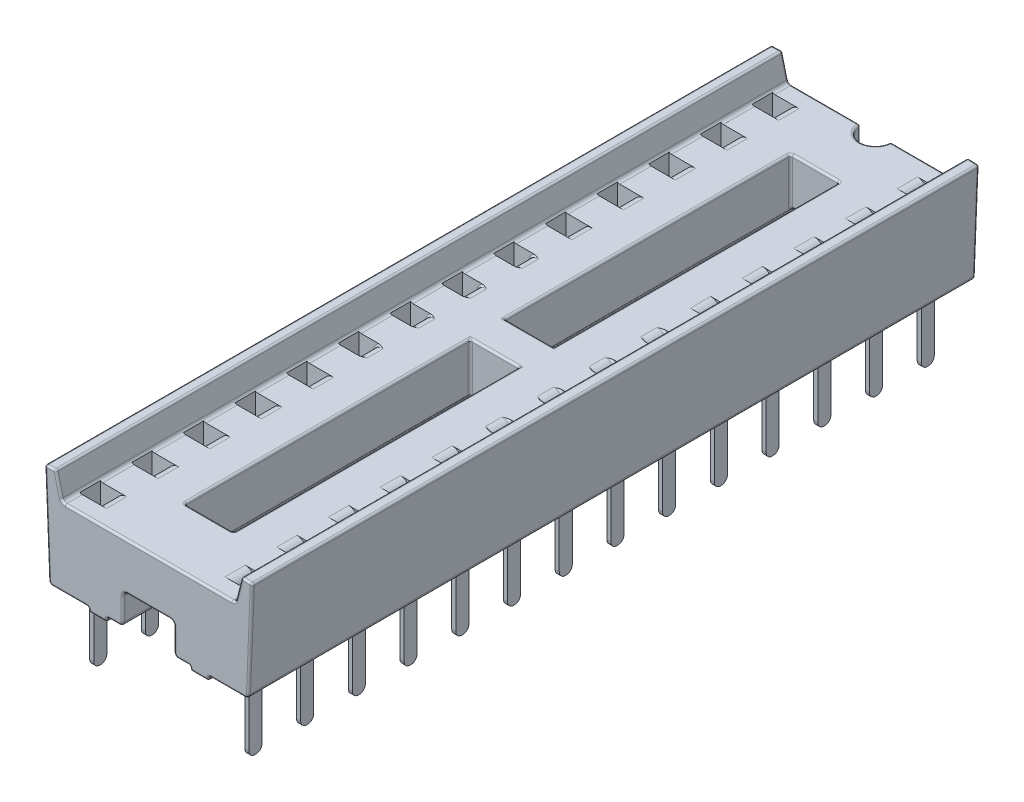
SolidWorks part; units mm, degrees
material "ABS"
ref_plane "Front Plane" through (0, 0, 0) normal (0, 0, 1) x (1, 0, 0)
ref_plane "Top Plane" through (0, 0, 0) normal (0, 1, 0) x (1, 0, 0)
ref_plane "Right Plane" through (0, 0, 0) normal (1, 0, 0) x (0, 0, -1)
sketch "Sketch1" plane through (0, 0, 0) normal (0, 0, 1) x (1, 0, 0)
  line L0 (-2.05, 0) -> (2.05, 0) construction
  line L1 (2.05, 0) -> (2.95, 0)
  line L2 (-2.05, 0) -> (-2.95, 0)
  line L3 (2.95, 0) -> (2.95, 0.2)
  line L4 (2.95, 0.2) -> (4.9, 0.2)
  line L5 (-2.95, 0) -> (-2.95, 0.2)
  line L6 (-2.95, 0.2) -> (-4.9, 0.2)
  line L7 (-2.05, 0) -> (-2.05, 0.2)
  line L8 (-2.05, 0.2) -> (-2.95, 0.2) construction
  line L9 (2.05, 0) -> (2.05, 0.2)
  line L10 (2.05, 0.2) -> (2.95, 0.2) construction
  line L11 (0, 0) -> (0, 1.7) construction
  line L12 (-1.25, 1.7) -> (1.25, 1.7)
  line L13 (-1.25, 1.7) -> (-1.25, 0.2)
  line L14 (-1.25, 0.2) -> (-2.05, 0.2)
  line L15 (1.25, 1.7) -> (1.25, 0.2)
  line L16 (1.25, 0.2) -> (2.05, 0.2)
  line L17 (-5.1, 5.2) -> (-4.5604, 5.2216)
  line L18 (-5.1, 5.2) -> (-5.1, 0.2) construction
  line L19 (-5.1, 0.2) -> (-4.9, 0.2) construction
  line L20 (4.9, 0.2) -> (5.1, 0.2) construction
  line L21 (-5.1, 5.2) -> (-4.9, 0.2)
  line L22 (4.9, 0.2) -> (5.1, 5.2)
  line L23 (5.1, 5.2) -> (5.1, 0.2) construction
  line L24 (5.1, 5.2) -> (4.5604, 5.2216)
  line L25 (0, 1.7) -> (0, 4) construction
  line L26 (-4.25, 4) -> (4.25, 4)
  line L27 (-4.5604, 5.2216) -> (-4.25, 4)
  line L28 (4.5604, 5.2216) -> (4.25, 4)
  dimension "D1" = 4.1
  dimension "D2" = 9.8
  dimension "D3" = 0.9
  dimension "D4" = 2.5
  dimension "D5" = 1.5
  dimension "D6" = 0.2
  dimension "D7" = 10.2
  dimension "D8" = 5
  dimension "D9" = 0.54
  dimension "D10" = 4
  dimension "D11" = 8.5
extrude "Boss-Extrude1" add sketch "Sketch1" along normal mid plane 35.7
fillet "Fillet5" radius 0.2 8 edges at (1.25, 0.2, 0) (4.9, 0.2, 0) (-4.9, 0.2, 0) (-1.25, 0.2, 0) (-1.25, 1.7, 0) (1.25, 1.7, 0) (4.25, 4, 0) (-4.25, 4, 0)
sketch "Sketch2" plane through (0, 4, 0) normal (0, 1, 0) x (1, 0, 0)
  line L1 (0, 0) -> (0, 17.85) construction
  line L2 (-1.2, 14.875) -> (1.2, 14.875)
  line L3 (-1.2, 14.875) -> (-1.2, -14.875)
  line L4 (-1.2, -14.875) -> (1.2, -14.875)
  line L5 (1.2, 14.875) -> (1.2, -14.875)
  line L6 (-1.2, 14.875) -> (1.2, -14.875) construction
  line L7 (-1.2, -14.875) -> (1.2, 14.875) construction
  line L8 (4.0945, 17.85) -> (-4.0945, 17.85) construction
  circle A0 centre (0, 17.85) radius 0.75
  point P2 (0, 0)
  dimension "D1" = 1.5
  dimension "D2" = 29.75
  dimension "D3" = 2.4
extrude "Cut-Extrude1" cut sketch "Sketch2" against normal up to surface (4 mm away) up to face at (-2.5, 0, 0)
sketch "Sketch3" plane through (0, 4, 0) normal (0, 1, 0) x (1, 0, 0)
  line L0 (0, 1.27) -> (0, -1.27) construction
  line L1 (0, 1.27) -> (0, 3.81) construction
  line L2 (0, -1.27) -> (0, -3.81) construction
  line L3 (-3.81, 1.27) -> (3.81, 1.27) construction
  line L4 (3.81, -1.27) -> (-3.81, -1.27) construction
  line L5 (-3.81, -3.81) -> (3.81, -3.81) construction
  line L6 (-3.81, 3.81) -> (3.81, 3.81) construction
  line L7 (0, 3.81) -> (0, 6.35) construction
  line L8 (-4.21, 4.31) -> (-3.41, 4.31)
  line L9 (-4.21, 4.31) -> (-4.21, 3.31)
  line L10 (-4.21, 3.31) -> (-3.41, 3.31)
  line L11 (-3.41, 4.31) -> (-3.41, 3.31)
  line L12 (-4.21, 4.31) -> (-3.41, 3.31) construction
  line L13 (-4.21, 3.31) -> (-3.41, 4.31) construction
  line L14 (-4.21, 1.77) -> (-3.41, 1.77)
  line L15 (-4.21, 1.77) -> (-4.21, 0.77)
  line L16 (-4.21, 0.77) -> (-3.41, 0.77)
  line L17 (-3.41, 1.77) -> (-3.41, 0.77)
  line L18 (-4.21, 1.77) -> (-3.41, 0.77) construction
  line L19 (-4.21, 0.77) -> (-3.41, 1.77) construction
  line L20 (-4.21, -0.77) -> (-3.41, -0.77)
  line L21 (-4.21, -0.77) -> (-4.21, -1.77)
  line L22 (-4.21, -1.77) -> (-3.41, -1.77)
  line L23 (-3.41, -0.77) -> (-3.41, -1.77)
  line L24 (-4.21, -0.77) -> (-3.41, -1.77) construction
  line L25 (-4.21, -1.77) -> (-3.41, -0.77) construction
  line L26 (-4.21, -3.31) -> (-3.41, -3.31)
  line L27 (-4.21, -3.31) -> (-4.21, -4.31)
  line L28 (-4.21, -4.31) -> (-3.41, -4.31)
  line L29 (-3.41, -3.31) -> (-3.41, -4.31)
  line L30 (-4.21, -3.31) -> (-3.41, -4.31) construction
  line L31 (-4.21, -4.31) -> (-3.41, -3.31) construction
  line L32 (4.21, -3.31) -> (3.41, -3.31)
  line L33 (4.21, -3.31) -> (4.21, -4.31)
  line L34 (4.21, -4.31) -> (3.41, -4.31)
  line L35 (3.41, -3.31) -> (3.41, -4.31)
  line L36 (4.21, -3.31) -> (3.41, -4.31) construction
  line L37 (4.21, -4.31) -> (3.41, -3.31) construction
  line L38 (4.21, -0.77) -> (3.41, -0.77)
  line L39 (4.21, -0.77) -> (4.21, -1.77)
  line L40 (4.21, -1.77) -> (3.41, -1.77)
  line L41 (3.41, -0.77) -> (3.41, -1.77)
  line L42 (4.21, -0.77) -> (3.41, -1.77) construction
  line L43 (4.21, -1.77) -> (3.41, -0.77) construction
  line L44 (4.21, 1.77) -> (3.41, 1.77)
  line L45 (4.21, 1.77) -> (4.21, 0.77)
  line L46 (4.21, 0.77) -> (3.41, 0.77)
  line L47 (3.41, 1.77) -> (3.41, 0.77)
  line L48 (4.21, 1.77) -> (3.41, 0.77) construction
  line L49 (4.21, 0.77) -> (3.41, 1.77) construction
  line L50 (4.21, 4.31) -> (3.41, 4.31)
  line L51 (4.21, 4.31) -> (4.21, 3.31)
  line L52 (4.21, 3.31) -> (3.41, 3.31)
  line L53 (3.41, 4.31) -> (3.41, 3.31)
  line L54 (4.21, 4.31) -> (3.41, 3.31) construction
  line L55 (4.21, 3.31) -> (3.41, 4.31) construction
  line L56 (0, 6.35) -> (0, 8.89) construction
  line L57 (0, 8.89) -> (0, 11.43) construction
  line L58 (0, 11.43) -> (0, 13.97) construction
  line L59 (0, 13.97) -> (0, 16.51) construction
  line L60 (0, -3.81) -> (0, -6.35) construction
  line L61 (0, -6.35) -> (0, -8.89) construction
  line L62 (0, -8.89) -> (0, -11.43) construction
  line L63 (0, -11.43) -> (0, -13.97) construction
  line L64 (0, -13.97) -> (0, -16.51) construction
  line L65 (-3.81, -6.35) -> (3.81, -6.35) construction
  line L66 (-3.81, -8.89) -> (3.81, -8.89) construction
  line L67 (-3.81, -11.43) -> (3.81, -11.43) construction
  line L68 (-3.81, -13.97) -> (3.81, -13.97) construction
  line L69 (-3.81, -16.51) -> (3.81, -16.51) construction
  line L70 (-3.81, 6.35) -> (3.81, 6.35) construction
  line L71 (-3.81, 8.89) -> (3.81, 8.89) construction
  line L72 (-3.81, 11.43) -> (3.81, 11.43) construction
  line L73 (-3.81, 13.97) -> (3.81, 13.97) construction
  line L74 (-3.81, 16.51) -> (3.81, 16.51) construction
  line L76 (4.21, -5.85) -> (3.41, -5.85)
  line L77 (4.21, -5.85) -> (4.21, -6.85)
  line L78 (4.21, -6.85) -> (3.41, -6.85)
  line L79 (3.41, -5.85) -> (3.41, -6.85)
  line L80 (4.21, -5.85) -> (3.41, -6.85) construction
  line L81 (4.21, -6.85) -> (3.41, -5.85) construction
  line L82 (4.21, -8.39) -> (3.41, -8.39)
  line L83 (4.21, -8.39) -> (4.21, -9.39)
  line L84 (4.21, -9.39) -> (3.41, -9.39)
  line L85 (3.41, -8.39) -> (3.41, -9.39)
  line L86 (4.21, -8.39) -> (3.41, -9.39) construction
  line L87 (4.21, -9.39) -> (3.41, -8.39) construction
  line L88 (4.21, -10.93) -> (3.41, -10.93)
  line L89 (4.21, -10.93) -> (4.21, -11.93)
  line L90 (4.21, -11.93) -> (3.41, -11.93)
  line L91 (3.41, -10.93) -> (3.41, -11.93)
  line L92 (4.21, -10.93) -> (3.41, -11.93) construction
  line L93 (4.21, -11.93) -> (3.41, -10.93) construction
  line L94 (4.21, -13.47) -> (3.41, -13.47)
  line L95 (4.21, -13.47) -> (4.21, -14.47)
  line L96 (4.21, -14.47) -> (3.41, -14.47)
  line L97 (3.41, -13.47) -> (3.41, -14.47)
  line L98 (4.21, -13.47) -> (3.41, -14.47) construction
  line L99 (4.21, -14.47) -> (3.41, -13.47) construction
  line L100 (4.21, -16.01) -> (3.41, -16.01)
  line L101 (4.21, -16.01) -> (4.21, -17.01)
  line L102 (4.21, -17.01) -> (3.41, -17.01)
  line L103 (3.41, -16.01) -> (3.41, -17.01)
  line L104 (4.21, -16.01) -> (3.41, -17.01) construction
  line L105 (4.21, -17.01) -> (3.41, -16.01) construction
  line L106 (-4.21, -5.85) -> (-3.41, -5.85)
  line L107 (-4.21, -5.85) -> (-4.21, -6.85)
  line L108 (-4.21, -6.85) -> (-3.41, -6.85)
  line L109 (-3.41, -5.85) -> (-3.41, -6.85)
  line L110 (-4.21, -5.85) -> (-3.41, -6.85) construction
  line L111 (-4.21, -6.85) -> (-3.41, -5.85) construction
  line L112 (-4.21, -8.39) -> (-3.41, -8.39)
  line L113 (-4.21, -8.39) -> (-4.21, -9.39)
  line L114 (-4.21, -9.39) -> (-3.41, -9.39)
  line L115 (-3.41, -8.39) -> (-3.41, -9.39)
  line L116 (-4.21, -8.39) -> (-3.41, -9.39) construction
  line L117 (-4.21, -9.39) -> (-3.41, -8.39) construction
  line L118 (-4.21, -10.93) -> (-3.41, -10.93)
  line L119 (-4.21, -10.93) -> (-4.21, -11.93)
  line L120 (-4.21, -11.93) -> (-3.41, -11.93)
  line L121 (-3.41, -10.93) -> (-3.41, -11.93)
  line L122 (-4.21, -10.93) -> (-3.41, -11.93) construction
  line L123 (-4.21, -11.93) -> (-3.41, -10.93) construction
  line L124 (-4.21, -13.47) -> (-3.41, -13.47)
  line L125 (-4.21, -13.47) -> (-4.21, -14.47)
  line L126 (-4.21, -14.47) -> (-3.41, -14.47)
  line L127 (-3.41, -13.47) -> (-3.41, -14.47)
  line L128 (-4.21, -13.47) -> (-3.41, -14.47) construction
  line L129 (-4.21, -14.47) -> (-3.41, -13.47) construction
  line L130 (-4.21, -16.01) -> (-3.41, -16.01)
  line L131 (-4.21, -16.01) -> (-4.21, -17.01)
  line L132 (-4.21, -17.01) -> (-3.41, -17.01)
  line L133 (-3.41, -16.01) -> (-3.41, -17.01)
  line L134 (-4.21, -16.01) -> (-3.41, -17.01) construction
  line L135 (-4.21, -17.01) -> (-3.41, -16.01) construction
  line L136 (-4.21, 6.85) -> (-3.41, 6.85)
  line L137 (-4.21, 6.85) -> (-4.21, 5.85)
  line L138 (-4.21, 5.85) -> (-3.41, 5.85)
  line L139 (-3.41, 6.85) -> (-3.41, 5.85)
  line L140 (-4.21, 6.85) -> (-3.41, 5.85) construction
  line L141 (-4.21, 5.85) -> (-3.41, 6.85) construction
  line L142 (4.21, 6.85) -> (3.41, 6.85)
  line L143 (4.21, 6.85) -> (4.21, 5.85)
  line L144 (4.21, 5.85) -> (3.41, 5.85)
  line L145 (3.41, 6.85) -> (3.41, 5.85)
  line L146 (4.21, 6.85) -> (3.41, 5.85) construction
  line L147 (4.21, 5.85) -> (3.41, 6.85) construction
  line L148 (4.21, 9.39) -> (3.41, 9.39)
  line L149 (4.21, 9.39) -> (4.21, 8.39)
  line L150 (4.21, 8.39) -> (3.41, 8.39)
  line L151 (3.41, 9.39) -> (3.41, 8.39)
  line L152 (4.21, 9.39) -> (3.41, 8.39) construction
  line L153 (4.21, 8.39) -> (3.41, 9.39) construction
  line L154 (4.21, 11.93) -> (3.41, 11.93)
  line L155 (4.21, 11.93) -> (4.21, 10.93)
  line L156 (4.21, 10.93) -> (3.41, 10.93)
  line L157 (3.41, 11.93) -> (3.41, 10.93)
  line L158 (4.21, 11.93) -> (3.41, 10.93) construction
  line L159 (4.21, 10.93) -> (3.41, 11.93) construction
  line L160 (-4.21, 9.39) -> (-3.41, 9.39)
  line L161 (-4.21, 9.39) -> (-4.21, 8.39)
  line L162 (-4.21, 8.39) -> (-3.41, 8.39)
  line L163 (-3.41, 9.39) -> (-3.41, 8.39)
  line L164 (-4.21, 9.39) -> (-3.41, 8.39) construction
  line L165 (-4.21, 8.39) -> (-3.41, 9.39) construction
  line L166 (-4.21, 11.93) -> (-3.41, 11.93)
  line L167 (-4.21, 11.93) -> (-4.21, 10.93)
  line L168 (-4.21, 10.93) -> (-3.41, 10.93)
  line L169 (-3.41, 11.93) -> (-3.41, 10.93)
  line L170 (-4.21, 11.93) -> (-3.41, 10.93) construction
  line L171 (-4.21, 10.93) -> (-3.41, 11.93) construction
  line L172 (-4.21, 14.47) -> (-3.41, 14.47)
  line L173 (-4.21, 14.47) -> (-4.21, 13.47)
  line L174 (-4.21, 13.47) -> (-3.41, 13.47)
  line L175 (-3.41, 14.47) -> (-3.41, 13.47)
  line L176 (-4.21, 14.47) -> (-3.41, 13.47) construction
  line L177 (-4.21, 13.47) -> (-3.41, 14.47) construction
  line L178 (4.21, 14.47) -> (3.41, 14.47)
  line L179 (4.21, 14.47) -> (4.21, 13.47)
  line L180 (4.21, 13.47) -> (3.41, 13.47)
  line L181 (3.41, 14.47) -> (3.41, 13.47)
  line L182 (4.21, 14.47) -> (3.41, 13.47) construction
  line L183 (4.21, 13.47) -> (3.41, 14.47) construction
  line L184 (-4.21, 17.01) -> (-3.41, 17.01)
  line L185 (-4.21, 17.01) -> (-4.21, 16.01)
  line L186 (-4.21, 16.01) -> (-3.41, 16.01)
  line L187 (-3.41, 17.01) -> (-3.41, 16.01)
  line L188 (-4.21, 17.01) -> (-3.41, 16.01) construction
  line L189 (-4.21, 16.01) -> (-3.41, 17.01) construction
  line L190 (4.21, 17.01) -> (3.41, 17.01)
  line L191 (4.21, 17.01) -> (4.21, 16.01)
  line L192 (4.21, 16.01) -> (3.41, 16.01)
  line L193 (3.41, 17.01) -> (3.41, 16.01)
  line L194 (4.21, 17.01) -> (3.41, 16.01) construction
  line L195 (4.21, 16.01) -> (3.41, 17.01) construction
  dimension "D1" = 2.54
  dimension "D2" = 7.62
  dimension "D3" = 0.8
  dimension "D4" = 1
extrude "Cut-Extrude2" cut sketch "Sketch3" against normal blind 3 and the other way through all
fillet "Fillet6" radius 0.1 12 edges at (-1.2, 2.8161, 14.875) (1.2, 2.8161, 14.875) (1.2, 2.8161, -14.875) (-1.2, 2.8161, -14.875) (-2.95, 0, 0) (-2.05, 0, 0) (2.05, 0, 0) (2.95, 0, 0) (5.1, 5.2, 0) (4.5604, 5.2216, 0) (-5.1, 5.2, 0) (-4.5604, 5.2216, 0)
fillet "Fillet7" radius 0.5 28 edges at (3.41, 4, -3.81) (3.41, 4, -1.27) (3.41, 4, 1.27) (3.41, 4, 3.81) (-3.41, 4, 3.81) (-3.41, 4, 1.27) (-3.41, 4, -1.27) (-3.41, 4, -3.81) (3.41, 4, -6.35) (3.41, 4, -8.89) (3.41, 4, -11.43) (3.41, 4, -13.97) (3.41, 4, -16.51) (-3.41, 4, -16.51) (3.41, 4, 16.51) (3.41, 4, 13.97) (3.41, 4, 11.43) (3.41, 4, 8.89) (3.41, 4, 6.35) (-3.41, 4, 16.51) (-3.41, 4, 13.97) (-3.41, 4, 11.43) (-3.41, 4, 8.89) (-3.41, 4, 6.35) (-3.41, 4, -13.97) (-3.41, 4, -11.43) (-3.41, 4, -8.89) (-3.41, 4, -6.35)
fillet "Fillet8" radius 0.1 6 edges at (2.95, 0.2, 0) (2.05, 0.2, 0) (-2.05, 0.2, 0) (-2.95, 0.2, 0) (-0.75, 2.85, -17.85) (0.75, 2.85, -17.85)
fillet "Fillet10" radius 0.1 132 edges at (3.41, 2.25, 4.31) (3.41, 2.25, 3.31) (3.41, 2.25, 1.77) (3.41, 2.25, 0.77) (3.41, 2.25, -0.77) (3.41, 2.25, -1.77) (3.41, 2.25, -3.31) (3.41, 2.25, -4.31) (-3.41, 2.25, -4.31) (-3.41, 2.25, -3.31) (-3.41, 2.25, -0.77) (-3.41, 2.25, -1.77) (-3.41, 2.25, 0.77) (-3.41, 2.25, 1.77) (-3.41, 2.25, 4.31) (-3.41, 2.25, 3.31) (1.0752, 1.6984, -14.875) (1.1867, 1.646, -14.8249) (1.2, 1.6323, 0) (1.1844, 1.6481, 14.8287) (1.0752, 1.6984, 14.875) (0, 1.7, 14.875) (-1.0752, 1.6984, 14.875) (-1.1867, 1.646, 14.8249) (-1.2, 1.6323, 0) (-1.1844, 1.6481, -14.8287) (-1.0752, 1.6984, -14.875) (-1.1707, 4, -14.8457) (0, 4, -14.875) (1.1707, 4, -14.8457) (1.2, 4, 0) (1.1707, 4, 14.8457) (0, 4, 14.875) (-1.1707, 4, 14.8457) (4.2172, 4.0421, 17.85) (4.4144, 4.6469, 17.85) (4.5776, 5.1986, 17.85) (4.8207, 5.2112, 17.85) (5.0696, 5.1719, 17.85) (5.0018, 2.746, 17.85) (4.8464, 0.2558, 17.85) (3.8789, 0.2, 17.85) (2.9793, 0.1707, 17.85) (2.9207, 0.0293, 17.85) (2.5, 0, 17.85) (2.0793, 0.0293, 17.85) (2.0207, 0.1707, 17.85) (1.7, 0.2, 17.85) (1.3086, 0.2586, 17.85) (1.25, 0.95, 17.85) (1.1914, 1.6414, 17.85) (0, 1.7, 17.85) (-1.1914, 1.6414, 17.85) (-1.25, 0.95, 17.85) (-1.3086, 0.2586, 17.85) (-1.7, 0.2, 17.85) (-2.0207, 0.1707, 17.85) (-2.0793, 0.0293, 17.85) (-2.5, 0, 17.85) (-2.9207, 0.0293, 17.85) (-2.9793, 0.1707, 17.85) (-3.8789, 0.2, 17.85) (-4.8464, 0.2558, 17.85) (-5.0018, 2.746, 17.85) (-5.0696, 5.1719, 17.85) (-4.8207, 5.2112, 17.85) (-4.5776, 5.1986, 17.85) (-4.4144, 4.6469, 17.85) (-4.2172, 4.0421, 17.85) (4.2172, 4.0421, -17.85) (4.4144, 4.6469, -17.85) (4.5776, 5.1986, -17.85) (4.8207, 5.2112, -17.85) (5.0696, 5.1719, -17.85) (5.0018, 2.746, -17.85) (4.8464, 0.2558, -17.85) (3.8789, 0.2, -17.85) (2.9793, 0.1707, -17.85) (2.9207, 0.0293, -17.85) (2.5, 0, -17.85) (2.0793, 0.0293, -17.85) (2.0207, 0.1707, -17.85) (1.7, 0.2, -17.85) (1.3086, 0.2586, -17.85) (1.25, 0.95, -17.85) (1.1914, 1.6414, -17.85) (0.947, 1.7, -17.85) (0.7777, 1.7, -17.8248) (0, 1.7, -17.1) (-0.7777, 1.7, -17.8248) (-0.947, 1.7, -17.85) (-1.1914, 1.6414, -17.85) (-1.25, 0.95, -17.85) (-1.3086, 0.2586, -17.85) (-1.7, 0.2, -17.85) (-2.0207, 0.1707, -17.85) (-2.0793, 0.0293, -17.85) (-2.5, 0, -17.85) (-2.9207, 0.0293, -17.85) (-2.9793, 0.1707, -17.85) (-3.8789, 0.2, -17.85) (-4.8464, 0.2558, -17.85) (-5.0018, 2.746, -17.85) (-5.0696, 5.1719, -17.85) (-4.8207, 5.2112, -17.85) (-4.5776, 5.1986, -17.85) (-4.4144, 4.6469, -17.85) (-4.2172, 4.0421, -17.85) (-2.4693, 4, -17.85) (-0.7777, 4, -17.8248) (0, 4, -17.1) (0.7777, 4, -17.8248) (3.2636, 3.8536, 4.31) (3.2636, 3.8536, 3.31) (3.2636, 3.8536, 1.77) (3.2636, 3.8536, 0.77) (3.2636, 3.8536, -0.77) (3.2636, 3.8536, -1.77) (3.2636, 3.8536, -3.31) (3.2636, 3.8536, -4.31) (-3.2636, 3.8536, -4.31) (-3.2636, 3.8536, -3.31) (-3.2636, 3.8536, -0.77) (-3.2636, 3.8536, -1.77) (-3.2636, 3.8536, 0.77) (-3.2636, 3.8536, 1.77) (-3.2636, 3.8536, 4.31) (-3.2636, 3.8536, 3.31) (0, 1.7, -14.875) (-1.2, 4, 0) (0, 4, 17.85) (2.4693, 4, -17.85)
sketch "Sketch4" plane through (0, 0.2, 0) normal (0, -1, 0) x (1, 0, 0)
  line L0 (0, 1.27) -> (0, -1.27) construction
  line L1 (0, 1.27) -> (0, 3.81) construction
  line L2 (0, -1.27) -> (0, -3.81) construction
  line L3 (-3.81, 1.27) -> (3.81, 1.27) construction
  line L4 (-3.81, -1.27) -> (3.81, -1.27) construction
  line L5 (-3.81, 3.81) -> (3.81, 3.81) construction
  line L6 (-3.81, -3.81) -> (3.81, -3.81) construction
  line L7 (0, -3.81) -> (0, -6.35) construction
  line L8 (3.71, 4.13) -> (3.91, 4.13)
  line L9 (3.71, 4.13) -> (3.71, 3.49)
  line L10 (3.71, 3.49) -> (3.91, 3.49)
  line L11 (3.91, 4.13) -> (3.91, 3.49)
  line L12 (3.71, 4.13) -> (3.91, 3.49) construction
  line L13 (3.71, 3.49) -> (3.91, 4.13) construction
  line L14 (3.71, 1.59) -> (3.91, 1.59)
  line L15 (3.71, 1.59) -> (3.71, 0.95)
  line L16 (3.71, 0.95) -> (3.91, 0.95)
  line L17 (3.91, 1.59) -> (3.91, 0.95)
  line L18 (3.71, 1.59) -> (3.91, 0.95) construction
  line L19 (3.71, 0.95) -> (3.91, 1.59) construction
  line L20 (3.71, -0.95) -> (3.91, -0.95)
  line L21 (3.71, -0.95) -> (3.71, -1.59)
  line L22 (3.71, -1.59) -> (3.91, -1.59)
  line L23 (3.91, -0.95) -> (3.91, -1.59)
  line L24 (3.71, -0.95) -> (3.91, -1.59) construction
  line L25 (3.71, -1.59) -> (3.91, -0.95) construction
  line L26 (3.71, -3.49) -> (3.91, -3.49)
  line L27 (3.71, -3.49) -> (3.71, -4.13)
  line L28 (3.71, -4.13) -> (3.91, -4.13)
  line L29 (3.91, -3.49) -> (3.91, -4.13)
  line L30 (3.71, -3.49) -> (3.91, -4.13) construction
  line L31 (3.71, -4.13) -> (3.91, -3.49) construction
  line L32 (-3.71, 4.13) -> (-3.91, 4.13)
  line L33 (-3.71, 4.13) -> (-3.71, 3.49)
  line L34 (-3.71, 3.49) -> (-3.91, 3.49)
  line L35 (-3.91, 4.13) -> (-3.91, 3.49)
  line L36 (-3.71, 4.13) -> (-3.91, 3.49) construction
  line L37 (-3.71, 3.49) -> (-3.91, 4.13) construction
  line L38 (-3.71, 1.59) -> (-3.91, 1.59)
  line L39 (-3.71, 1.59) -> (-3.71, 0.95)
  line L40 (-3.71, 0.95) -> (-3.91, 0.95)
  line L41 (-3.91, 1.59) -> (-3.91, 0.95)
  line L42 (-3.71, 1.59) -> (-3.91, 0.95) construction
  line L43 (-3.71, 0.95) -> (-3.91, 1.59) construction
  line L44 (-3.71, -0.95) -> (-3.91, -0.95)
  line L45 (-3.71, -0.95) -> (-3.71, -1.59)
  line L46 (-3.71, -1.59) -> (-3.91, -1.59)
  line L47 (-3.91, -0.95) -> (-3.91, -1.59)
  line L48 (-3.71, -0.95) -> (-3.91, -1.59) construction
  line L49 (-3.71, -1.59) -> (-3.91, -0.95) construction
  line L50 (-3.71, -3.49) -> (-3.91, -3.49)
  line L51 (-3.71, -3.49) -> (-3.71, -4.13)
  line L52 (-3.71, -4.13) -> (-3.91, -4.13)
  line L53 (-3.91, -3.49) -> (-3.91, -4.13)
  line L54 (-3.71, -3.49) -> (-3.91, -4.13) construction
  line L55 (-3.71, -4.13) -> (-3.91, -3.49) construction
  line L56 (0, -6.35) -> (0, -8.89) construction
  line L57 (0, -8.89) -> (0, -11.43) construction
  line L58 (0, -11.43) -> (0, -13.97) construction
  line L59 (0, -13.97) -> (0, -16.51) construction
  line L60 (0, 3.81) -> (0, 6.35) construction
  line L61 (0, 6.35) -> (0, 8.89) construction
  line L62 (0, 8.89) -> (0, 11.43) construction
  line L63 (0, 11.43) -> (0, 13.97) construction
  line L64 (0, 13.97) -> (0, 16.51) construction
  line L65 (-3.81, 6.35) -> (3.81, 6.35) construction
  line L66 (-3.81, 8.89) -> (3.81, 8.89) construction
  line L67 (-3.81, 11.43) -> (3.81, 11.43) construction
  line L68 (-3.81, 13.97) -> (3.81, 13.97) construction
  line L69 (-3.81, 16.51) -> (3.81, 16.51) construction
  line L70 (-3.81, -6.35) -> (3.81, -6.35) construction
  line L71 (-3.81, -8.89) -> (3.81, -8.89) construction
  line L72 (-3.81, -11.43) -> (3.81, -11.43) construction
  line L73 (-3.81, -13.97) -> (3.81, -13.97) construction
  line L74 (-3.81, -16.51) -> (3.81, -16.51) construction
  line L76 (-3.91, -6.03) -> (-3.71, -6.03)
  line L77 (-3.91, -6.03) -> (-3.91, -6.67)
  line L78 (-3.91, -6.67) -> (-3.71, -6.67)
  line L79 (-3.71, -6.03) -> (-3.71, -6.67)
  line L80 (-3.91, -6.03) -> (-3.71, -6.67) construction
  line L81 (-3.91, -6.67) -> (-3.71, -6.03) construction
  line L82 (-3.91, -8.57) -> (-3.71, -8.57)
  line L83 (-3.91, -8.57) -> (-3.91, -9.21)
  line L84 (-3.91, -9.21) -> (-3.71, -9.21)
  line L85 (-3.71, -8.57) -> (-3.71, -9.21)
  line L86 (-3.91, -8.57) -> (-3.71, -9.21) construction
  line L87 (-3.91, -9.21) -> (-3.71, -8.57) construction
  line L88 (-3.91, -11.11) -> (-3.71, -11.11)
  line L89 (-3.91, -11.11) -> (-3.91, -11.75)
  line L90 (-3.91, -11.75) -> (-3.71, -11.75)
  line L91 (-3.71, -11.11) -> (-3.71, -11.75)
  line L92 (-3.91, -11.11) -> (-3.71, -11.75) construction
  line L93 (-3.91, -11.75) -> (-3.71, -11.11) construction
  line L94 (3.71, -6.03) -> (3.91, -6.03)
  line L95 (3.71, -6.03) -> (3.71, -6.67)
  line L96 (3.71, -6.67) -> (3.91, -6.67)
  line L97 (3.91, -6.03) -> (3.91, -6.67)
  line L98 (3.71, -6.03) -> (3.91, -6.67) construction
  line L99 (3.71, -6.67) -> (3.91, -6.03) construction
  line L100 (3.71, -8.57) -> (3.91, -8.57)
  line L101 (3.71, -8.57) -> (3.71, -9.21)
  line L102 (3.71, -9.21) -> (3.91, -9.21)
  line L103 (3.91, -8.57) -> (3.91, -9.21)
  line L104 (3.71, -8.57) -> (3.91, -9.21) construction
  line L105 (3.71, -9.21) -> (3.91, -8.57) construction
  line L106 (3.71, -11.11) -> (3.91, -11.11)
  line L107 (3.71, -11.11) -> (3.71, -11.75)
  line L108 (3.71, -11.75) -> (3.91, -11.75)
  line L109 (3.91, -11.11) -> (3.91, -11.75)
  line L110 (3.71, -11.11) -> (3.91, -11.75) construction
  line L111 (3.71, -11.75) -> (3.91, -11.11) construction
  line L112 (3.71, -13.65) -> (3.91, -13.65)
  line L113 (3.71, -13.65) -> (3.71, -14.29)
  line L114 (3.71, -14.29) -> (3.91, -14.29)
  line L115 (3.91, -13.65) -> (3.91, -14.29)
  line L116 (3.71, -13.65) -> (3.91, -14.29) construction
  line L117 (3.71, -14.29) -> (3.91, -13.65) construction
  line L118 (3.71, -16.19) -> (3.91, -16.19)
  line L119 (3.71, -16.19) -> (3.71, -16.83)
  line L120 (3.71, -16.83) -> (3.91, -16.83)
  line L121 (3.91, -16.19) -> (3.91, -16.83)
  line L122 (3.71, -16.19) -> (3.91, -16.83) construction
  line L123 (3.71, -16.83) -> (3.91, -16.19) construction
  line L124 (-3.71, -13.65) -> (-3.91, -13.65)
  line L125 (-3.71, -13.65) -> (-3.71, -14.29)
  line L126 (-3.71, -14.29) -> (-3.91, -14.29)
  line L127 (-3.91, -13.65) -> (-3.91, -14.29)
  line L128 (-3.71, -13.65) -> (-3.91, -14.29) construction
  line L129 (-3.71, -14.29) -> (-3.91, -13.65) construction
  line L130 (-3.71, -16.19) -> (-3.91, -16.19)
  line L131 (-3.71, -16.19) -> (-3.71, -16.83)
  line L132 (-3.71, -16.83) -> (-3.91, -16.83)
  line L133 (-3.91, -16.19) -> (-3.91, -16.83)
  line L134 (-3.71, -16.19) -> (-3.91, -16.83) construction
  line L135 (-3.71, -16.83) -> (-3.91, -16.19) construction
  line L136 (-3.71, 6.67) -> (-3.91, 6.67)
  line L137 (-3.71, 6.67) -> (-3.71, 6.03)
  line L138 (-3.71, 6.03) -> (-3.91, 6.03)
  line L139 (-3.91, 6.67) -> (-3.91, 6.03)
  line L140 (-3.71, 6.67) -> (-3.91, 6.03) construction
  line L141 (-3.71, 6.03) -> (-3.91, 6.67) construction
  line L142 (3.71, 6.67) -> (3.91, 6.67)
  line L143 (3.71, 6.67) -> (3.71, 6.03)
  line L144 (3.71, 6.03) -> (3.91, 6.03)
  line L145 (3.91, 6.67) -> (3.91, 6.03)
  line L146 (3.71, 6.67) -> (3.91, 6.03) construction
  line L147 (3.71, 6.03) -> (3.91, 6.67) construction
  line L148 (3.71, 9.21) -> (3.91, 9.21)
  line L149 (3.71, 9.21) -> (3.71, 8.57)
  line L150 (3.71, 8.57) -> (3.91, 8.57)
  line L151 (3.91, 9.21) -> (3.91, 8.57)
  line L152 (3.71, 9.21) -> (3.91, 8.57) construction
  line L153 (3.71, 8.57) -> (3.91, 9.21) construction
  line L154 (-3.71, 9.21) -> (-3.91, 9.21)
  line L155 (-3.71, 9.21) -> (-3.71, 8.57)
  line L156 (-3.71, 8.57) -> (-3.91, 8.57)
  line L157 (-3.91, 9.21) -> (-3.91, 8.57)
  line L158 (-3.71, 9.21) -> (-3.91, 8.57) construction
  line L159 (-3.71, 8.57) -> (-3.91, 9.21) construction
  line L160 (-3.71, 11.75) -> (-3.91, 11.75)
  line L161 (-3.71, 11.75) -> (-3.71, 11.11)
  line L162 (-3.71, 11.11) -> (-3.91, 11.11)
  line L163 (-3.91, 11.75) -> (-3.91, 11.11)
  line L164 (-3.71, 11.75) -> (-3.91, 11.11) construction
  line L165 (-3.71, 11.11) -> (-3.91, 11.75) construction
  line L166 (-3.71, 14.29) -> (-3.91, 14.29)
  line L167 (-3.71, 14.29) -> (-3.71, 13.65)
  line L168 (-3.71, 13.65) -> (-3.91, 13.65)
  line L169 (-3.91, 14.29) -> (-3.91, 13.65)
  line L170 (-3.71, 14.29) -> (-3.91, 13.65) construction
  line L171 (-3.71, 13.65) -> (-3.91, 14.29) construction
  line L172 (-3.71, 16.83) -> (-3.91, 16.83)
  line L173 (-3.71, 16.83) -> (-3.71, 16.19)
  line L174 (-3.71, 16.19) -> (-3.91, 16.19)
  line L175 (-3.91, 16.83) -> (-3.91, 16.19)
  line L176 (-3.71, 16.83) -> (-3.91, 16.19) construction
  line L177 (-3.71, 16.19) -> (-3.91, 16.83) construction
  line L178 (3.71, 11.75) -> (3.91, 11.75)
  line L179 (3.71, 11.75) -> (3.71, 11.11)
  line L180 (3.71, 11.11) -> (3.91, 11.11)
  line L181 (3.91, 11.75) -> (3.91, 11.11)
  line L182 (3.71, 11.75) -> (3.91, 11.11) construction
  line L183 (3.71, 11.11) -> (3.91, 11.75) construction
  line L184 (3.71, 14.29) -> (3.91, 14.29)
  line L185 (3.71, 14.29) -> (3.71, 13.65)
  line L186 (3.71, 13.65) -> (3.91, 13.65)
  line L187 (3.91, 14.29) -> (3.91, 13.65)
  line L188 (3.71, 14.29) -> (3.91, 13.65) construction
  line L189 (3.71, 13.65) -> (3.91, 14.29) construction
  line L190 (3.71, 16.83) -> (3.91, 16.83)
  line L191 (3.71, 16.83) -> (3.71, 16.19)
  line L192 (3.71, 16.19) -> (3.91, 16.19)
  line L193 (3.91, 16.83) -> (3.91, 16.19)
  line L194 (3.71, 16.83) -> (3.91, 16.19) construction
  line L195 (3.71, 16.19) -> (3.91, 16.83) construction
  dimension "D1" = 2.54
  dimension "D2" = 0.2
  dimension "D3" = 0.64
  dimension "D4" = 7.62
extrude "Boss-Extrude2" add sketch "Sketch4" along normal blind 3.5
fillet "Fillet11" radius 0.3 56 edges at (3.81, -3.3, 4.13) (3.81, -3.3, 3.49) (3.81, -3.3, 1.59) (3.81, -3.3, 0.95) (3.81, -3.3, -0.95) (3.81, -3.3, -1.59) (3.81, -3.3, -3.49) (3.81, -3.3, -4.13) (-3.81, -3.3, -4.13) (-3.81, -3.3, -3.49) (-3.81, -3.3, -1.59) (-3.81, -3.3, -0.95) (-3.81, -3.3, 0.95) (-3.81, -3.3, 1.59) (-3.81, -3.3, 3.49) (-3.81, -3.3, 4.13) (-3.81, -3.3, -16.83) (-3.81, -3.3, -16.19) (-3.81, -3.3, -14.29) (-3.81, -3.3, -13.65) (-3.81, -3.3, -11.75) (-3.81, -3.3, -11.11) (-3.81, -3.3, -9.21) (-3.81, -3.3, -8.57) (-3.81, -3.3, -6.67) (-3.81, -3.3, -6.03) (-3.81, -3.3, 16.83) (-3.81, -3.3, 16.19) (-3.81, -3.3, 14.29) (-3.81, -3.3, 13.65) (-3.81, -3.3, 11.75) (-3.81, -3.3, 11.11) (-3.81, -3.3, 9.21) (-3.81, -3.3, 8.57) (-3.81, -3.3, 6.67) (-3.81, -3.3, 6.03) (3.81, -3.3, -16.83) (3.81, -3.3, -16.19) (3.81, -3.3, -14.29) (3.81, -3.3, -13.65) (3.81, -3.3, -11.75) (3.81, -3.3, -11.11) (3.81, -3.3, -9.21) (3.81, -3.3, -8.57) (3.81, -3.3, -6.67) (3.81, -3.3, -6.03) (3.81, -3.3, 6.03) (3.81, -3.3, 6.67) (3.81, -3.3, 8.57) (3.81, -3.3, 9.21) (3.81, -3.3, 11.11) (3.81, -3.3, 11.75) (3.81, -3.3, 13.65) (3.81, -3.3, 14.29) (3.81, -3.3, 16.19) (3.81, -3.3, 16.83)
sketch "Sketch5" plane through (0, 4, 0) normal (0, 1, 0) x (1, 0, 0)
  line L1 (-1.7, 0.85) -> (1.7, 0.85)
  line L2 (-1.7, 0.85) -> (-1.7, -0.85)
  line L3 (-1.7, -0.85) -> (1.7, -0.85)
  line L4 (1.7, 0.85) -> (1.7, -0.85)
  line L5 (-1.7, 0.85) -> (1.7, -0.85) construction
  line L6 (-1.7, -0.85) -> (1.7, 0.85) construction
  point P0 (0, 0)
  dimension "D1" = 1.7
  dimension "D2" = 3.4
extrude "Boss-Extrude3" add sketch "Sketch5" against normal up to surface (3.8 mm away) up to face at (-1.7, 0.2, 0)
fillet "Fillet12" radius 0.1 4 edges at (0, 4, -0.85) (0, 4, 0.85) (0, 0.2, 0.85) (0, 0.2, -0.85)
fillet "Fillet13" radius 0.1 28 edges at (1.3514, 0.226, -0.8173) (1.2568, 0.3482, -0.85) (1.25, 0.95, -0.85) (1.2415, 1.5577, -0.85) (1.2043, 1.637, -0.85) (1.2293, 3.9707, -0.8207) (1.2293, 3.9707, 0.8207) (1.3514, 0.226, 0.8173) (1.2568, 0.3482, 0.85) (1.25, 0.95, 0.85) (1.2415, 1.5577, 0.85) (1.2043, 1.637, 0.85) (-1.3514, 0.226, 0.8173) (-1.2568, 0.3482, 0.85) (-1.25, 0.95, 0.85) (-1.2415, 1.5577, 0.85) (-1.2043, 1.637, 0.85) (-1.2293, 3.9707, 0.8207) (-1.2293, 3.9707, -0.8207) (-1.3514, 0.226, -0.8173) (-1.2568, 0.3482, -0.85) (-1.25, 0.95, -0.85) (-1.2415, 1.5577, -0.85) (-1.2043, 1.637, -0.85) (1.2, 2.7829, -0.85) (1.2, 2.7829, 0.85) (-1.2, 2.7829, 0.85) (-1.2, 2.7829, -0.85)
